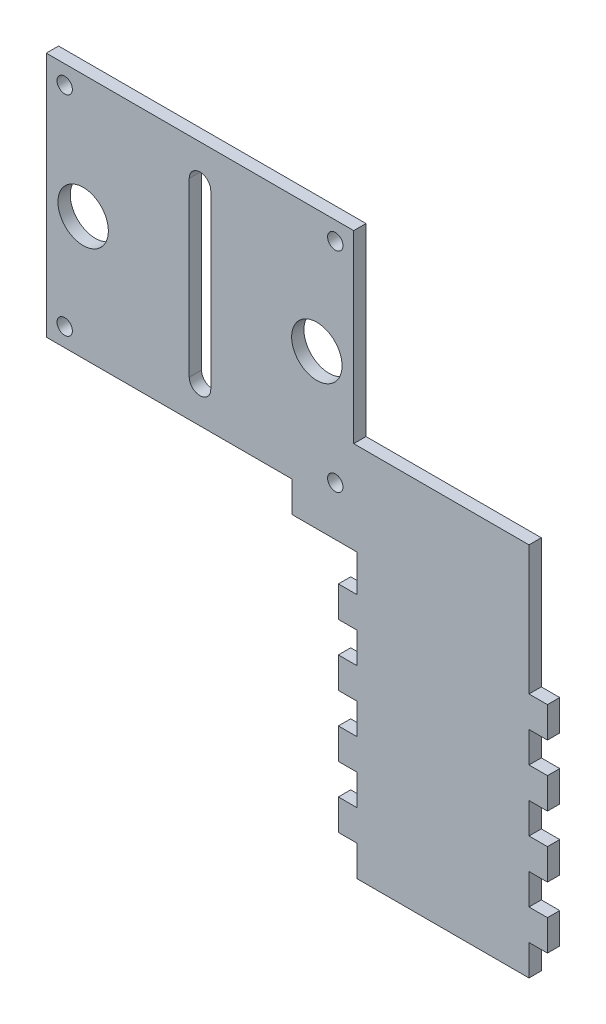
SolidWorks part; units mm, degrees
ref_plane "Front Plane" through (0, 0, 0) normal (0, 0, 1) x (1, 0, 0)
ref_plane "Top Plane" through (0, 0, 0) normal (0, 1, 0) x (1, 0, 0)
ref_plane "Right Plane" through (0, 0, 0) normal (1, 0, 0) x (0, 0, -1)
sketch "Sketch1" plane through (0, 0, 0) normal (0, 0, 1) x (1, 0, 0)
  line L1 (0, 0) -> (50, 0)
  line L2 (0, 0) -> (0, 40)
  line L3 (0, 40) -> (50, 40)
  line L4 (50, 0) -> (50, 40)
  line L5 (50, 0) -> (78.5, 0)
  line L6 (50, 0) -> (50, -51)
  line L7 (50, -51) -> (78.5, -51)
  line L8 (78.5, 0) -> (78.5, -51)
  line L9 (50, 0) -> (78.5, 0)
  line L12 (78.5, 0) -> (78.5, -21)
  line L13 (78.5, 0) -> (50, 0)
  line L14 (78.5, 0) -> (78.5, 10)
  line L15 (78.5, 10) -> (50, 10)
  line L16 (50, 0) -> (50, 10)
  line L17 (40, 0) -> (50, 0)
  line L18 (40, 0) -> (40, -5)
  line L19 (40, -5) -> (50, -5)
  line L20 (50, 0) -> (50, -5)
  dimension "D1" = 50
  dimension "D2" = 40
  dimension "D3" = 28.5
  dimension "D4" = 51
  dimension "D5" = 0
  dimension "D6" = 10
  dimension "D7" = 0
  dimension "D8" = 0
  dimension "D9" = 0
  dimension "D10" = 10
  dimension "D11" = 5
extrude "plate_body" add sketch "Sketch1" along normal blind 2 contours L1 L4 L3 L2 | L8 L5 L1 L6 L7 | L14 L15 L4 L5 | L18 L19 L6 L1 region at (25, 20, 0) region at (45, -2.5, 0) region at (64.25, 5, 0) region at (64.25, -25.5, 0)
sketch "Sketch2" plane through (0, 0, 2) normal (0, 0, 1) x (1, 0, 0)
  line L2 (0, 0) -> (0, 40) construction
  line L3 (0, 40) -> (50, 40) construction
  circle A0 centre (6, 20) radius 4.1
  circle A1 centre (44, 20) radius 4.1
  dimension "D1" = 38
  dimension "D2" = 8.2
  dimension "D3" = 8.2
  dimension "D4" = 6
  dimension "D5" = 20
  dimension "D6" = 20
extrude "shaft_bearings" cut sketch "Sketch2" against normal through all
sketch "Sketch4" plane through (0, 0, 2) normal (0, 0, 1) x (1, 0, 0)
  line L0 (25, 34) -> (25, 6) construction
  line L1 (26.75, 34) -> (26.75, 6)
  line L2 (23.25, 34) -> (23.25, 6)
  line L3 (0, 0) -> (40, 0) construction
  line L5 (0, 0) -> (0, 40) construction
  arc A0 (26.75, 34) -> (23.25, 34) centre (25, 34) ccw
  arc A1 (23.25, 6) -> (26.75, 6) centre (25, 6) ccw
  point P2 (25, 20)
  dimension "D4" = 6
  dimension "D1" = 3.5
  dimension "D2" = 28
  dimension "D3" = 25
extrude "slot" cut sketch "Sketch4" against normal through all
sketch "Sketch5" plane through (0, 0, 2) normal (0, 0, 1) x (1, 0, 0)
  line L0 (0, 40) -> (50, 40) construction
  line L1 (0, 0) -> (0, 40) construction
  line L3 (50, 10) -> (50, 40) construction
  line L4 (0, 0) -> (40, 0) construction
  circle A0 centre (3, 37) radius 1.25
  circle A1 centre (47, 37) radius 1.25
  circle A2 centre (3, 3) radius 1.25
  circle A3 centre (47, 3) radius 1.25
  dimension "D1" = 2.5
  dimension "D2" = 2.5
  dimension "D3" = 2.5
  dimension "D4" = 2.5
  dimension "D5" = 3
  dimension "D6" = 3
  dimension "D7" = 3
  dimension "D8" = 3
  dimension "D9" = 3
  dimension "D10" = 3
  dimension "D11" = 3
  dimension "D12" = 3
extrude "bolt_holes" cut sketch "Sketch5" against normal through all
sketch "Sketch6" plane through (0, 0, 2) normal (0, 0, 1) x (1, 0, 0)
  line L0 (50, -51) -> (78.5, -51) construction
  line L1 (50, -5) -> (50.5, -5)
  line L2 (50, -5) -> (50, -51)
  line L3 (50, -51) -> (50.5, -51)
  line L4 (50.5, -5) -> (50.5, -51)
  dimension "D1" = 0.5
extrude "Cut-Extrude1" cut sketch "Sketch6" against normal through all
sketch "Sketch8" plane through (0, 0, 2) normal (0, 0, 1) x (1, 0, 0)
  line L0 (50.5, -36) -> (47.5, -36)
  line L1 (50.5, -46) -> (47.5, -46)
  line L2 (50.5, -46) -> (50.5, -41)
  line L3 (50.5, -41) -> (47.5, -41)
  line L4 (47.5, -46) -> (47.5, -41)
  line L5 (78.5, -46) -> (81.5, -46)
  line L6 (78.5, -46) -> (78.5, -41)
  line L7 (78.5, -41) -> (81.5, -41)
  line L8 (81.5, -46) -> (81.5, -41)
  line L9 (50.5, -36) -> (50.5, -31)
  line L10 (50.5, -31) -> (47.5, -31)
  line L11 (47.5, -36) -> (47.5, -31)
  line L12 (78.5, -36) -> (81.5, -36)
  line L13 (78.5, -36) -> (78.5, -31)
  line L14 (78.5, -31) -> (81.5, -31)
  line L15 (81.5, -36) -> (81.5, -31)
  line L16 (50.5, -51) -> (50.5, -5) construction
  line L17 (78.5, -51) -> (78.5, 10) construction
  line L18 (50.5, -16) -> (47.5, -16)
  line L19 (50.5, -26) -> (47.5, -26)
  line L20 (50.5, -26) -> (50.5, -21)
  line L21 (50.5, -21) -> (47.5, -21)
  line L22 (47.5, -26) -> (47.5, -21)
  line L23 (78.5, -26) -> (81.5, -26)
  line L24 (78.5, -26) -> (78.5, -21)
  line L25 (78.5, -21) -> (81.5, -21)
  line L26 (81.5, -26) -> (81.5, -21)
  line L27 (50.5, -16) -> (50.5, -11)
  line L28 (50.5, -11) -> (47.5, -11)
  line L29 (47.5, -16) -> (47.5, -11)
  line L30 (78.5, -16) -> (81.5, -16)
  line L31 (78.5, -16) -> (78.5, -11)
  line L32 (78.5, -11) -> (81.5, -11)
  line L33 (81.5, -16) -> (81.5, -11)
  line L34 (50.5, -51) -> (78.5, -51) construction
  point P38 (80, -31)
  point P41 (80, -41)
  dimension "D1" = 5
  dimension "D2" = 5
  dimension "D3" = 3
  dimension "D4" = 3
  dimension "D5" = 5
  dimension "D6" = 5
  dimension "D7" = 3
  dimension "D8" = 3
  dimension "D9" = 0
  dimension "D10" = 0
  dimension "D11" = 5
  dimension "D12" = 5
  dimension "D13" = 5
  dimension "D14" = 5
  dimension "D15" = 3
  dimension "D16" = 3
  dimension "D17" = 5
  dimension "D18" = 5
  dimension "D19" = 3
  dimension "D20" = 3
  dimension "D21" = 5
  dimension "D22" = 5
  dimension "D25" = 0
  dimension "D26" = 0
  dimension "D27" = 5
  dimension "D28" = 5
  dimension "D29" = 10
  dimension "D30" = 10
extrude "finger_joints" add sketch "Sketch8" along direction (0, 0, 1) on the side against the normal up to surface (2 mm away) up to face at (48.25, 37, 0)
